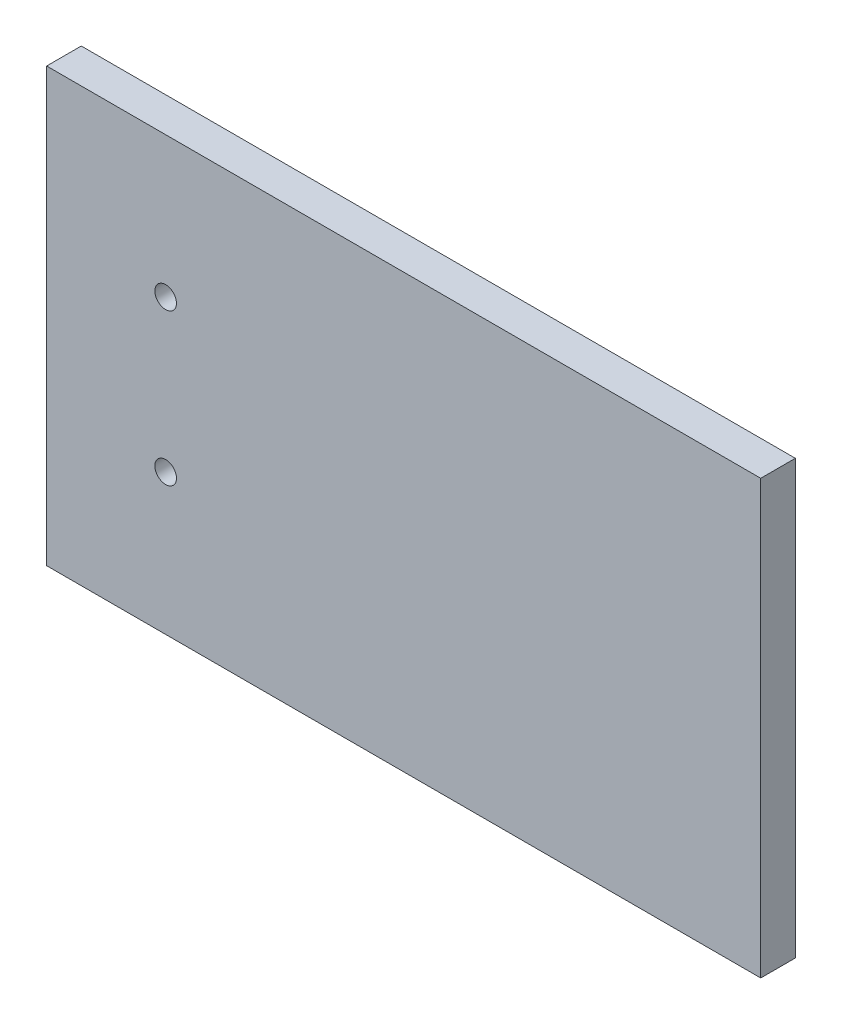
SolidWorks part; units mm, degrees
ref_plane "Front Plane" through (0, 0, 0) normal (0, 0, 1) x (1, 0, 0)
ref_plane "Top Plane" through (0, 0, 0) normal (0, 1, 0) x (1, 0, 0)
ref_plane "Right Plane" through (0, 0, 0) normal (1, 0, 0) x (0, 0, -1)
sketch "Sketch1" plane through (0, 0, 0) normal (0, 1, 0) x (1, 0, 0)
  line L0 (-6, 0) -> (6, 0) construction
  line L1 (6, -20) -> (-6, -20)
  line L2 (6, -20) -> (6, 20)
  line L3 (6, 20) -> (-6, 20)
  line L4 (-6, -20) -> (-6, 20)
  line L5 (6, -20) -> (-6, 20) construction
  line L6 (6, 20) -> (-6, -20) construction
  line L7 (0, -5) -> (0, 5) construction
  circle A0 centre (0, 5) radius 1
  circle A1 centre (0, -5) radius 1
  point P0 (0, 0)
  dimension "D3" = 5
  dimension "D4" = 2
  dimension "D1" = 40
  dimension "D2" = 12
extrude "Hinge " [suppressed] add sketch "Sketch1" along normal blind 5
sketch "Sketch2" [suppressed] plane through (6, 0, 0) normal (1, 0, 0) x (0, 0, -1)
  line L0 (0, 0) -> (0, 5) construction
  line L1 (-20, 0) -> (20, 0) construction
  line L2 (-20, 5) -> (20, 5) construction
  line L3 (-20, 2.5) -> (20, 2.5) construction
  line L4 (-20, 5) -> (-20, 0) construction
  line L5 (20, 5) -> (20, 0) construction
  line L7 (-6, 0) -> (-16, 0)
  line L8 (-6, 0) -> (-6, 5)
  line L9 (-6, 5) -> (-16, 5)
  line L10 (-16, 0) -> (-16, 5)
  line L11 (-6, 0) -> (-16, 5) construction
  line L12 (-6, 5) -> (-16, 0) construction
  line L13 (16, 0) -> (6, 0)
  line L14 (16, 0) -> (16, 5)
  line L15 (16, 5) -> (6, 5)
  line L16 (6, 0) -> (6, 5)
  line L17 (16, 0) -> (6, 5) construction
  line L18 (16, 5) -> (6, 0) construction
  point P12 (-11, 2.5)
  point P17 (11, 2.5)
  dimension "D1" = 6
  dimension "D2" = 5
  dimension "D3" = 10
extrude "Hinge Extrude 1" [suppressed] add sketch "Sketch2" along normal blind 5
sketch "Sketch3" [suppressed] plane through (0, 0, -16) normal (0, 0, -1) x (-1, 0, 0)
  line L0 (-8.5, 0) -> (-8.5, 5) construction
  line L1 (-11, 0) -> (-6, 0) construction
  line L2 (-11, 5) -> (-6, 5) construction
  circle A0 centre (-8.5, 2.5) radius 1
  dimension "D1" = 2
extrude "Hole Cut 1" [suppressed] cut sketch "Sketch3" against normal through all both and the other way through all
fillet "Fillet Holes 1" [suppressed] radius 0.5
chamfer "Chamfer 1" [suppressed] distance 1.5 angle 45
sketch "Sketch4" [suppressed] plane through (6, 0, 0) normal (1, 0, 0) x (0, 0, -1)
  line L0 (0, 0) -> (0, 5) construction
  line L1 (-20, 0) -> (20, 0) construction
  line L2 (-20, 5) -> (20, 5) construction
  line L4 (5, 0) -> (-5, 0)
  line L5 (5, 0) -> (5, 5)
  line L6 (5, 5) -> (-5, 5)
  line L7 (-5, 0) -> (-5, 5)
  line L8 (5, 0) -> (-5, 5) construction
  line L9 (5, 5) -> (-5, 0) construction
  point P6 (0, 2.5)
  dimension "D1" = 5
  dimension "D2" = 10
extrude "Hinge Extrude 2" [suppressed] add sketch "Sketch4" along normal blind 5
sketch "Sketch6" [suppressed] plane through (0, 0, -5) normal (0, 0, -1) x (-1, 0, 0)
  line L0 (-8.5, 0) -> (-8.5, 5) construction
  line L1 (-11, 0) -> (-6, 0) construction
  line L2 (-11, 5) -> (-6, 5) construction
  circle A0 centre (-8.5, 2.5) radius 1
  dimension "D1" = 2
extrude "Hole Cut 2 " [suppressed] cut sketch "Sketch6" against normal through all
chamfer "Chamfer2" [suppressed] distance 1.5 angle 45
fillet "Fillet Holes 2" [suppressed] radius 0.5
sketch "Sketch7" [suppressed] plane through (0, 0, 0) normal (0, 0, 1) x (1, 0, 0)
  circle A0 centre (0, 0) radius 1
  dimension "D1" = 2
extrude "Hinge Bar" [suppressed] add sketch "Sketch7" along normal blind 42
sketch "Sketch8" [suppressed] plane through (0, 0, 0) normal (0, 0, -1) x (-1, 0, 0)
  circle A0 centre (0, 0) radius 1.5
  dimension "D1" = 3
extrude "Hinge Bar Holder" [suppressed] add sketch "Sketch8" along normal blind 1
chamfer "Hinge Bar Holder Fillet" [suppressed] distance 0.5 angle 45
sketch "Sketch9" plane through (0, 0, 0) normal (1, 0, 0) x (0, 0, -1)
  circle A0 centre (0, 0) radius 1.5
  dimension "D1" = 3
extrude "Hinge Bar Cap" [suppressed] add sketch "Sketch9" along normal blind 2
chamfer "Hinge Bar Cap Fillet" [suppressed] distance 0.5 angle 45
sketch "Sketch10" [suppressed] plane through (2, 0, 0) normal (1, 0, 0) x (0, 0, -1)
  circle A0 centre (0, 0) radius 1
  dimension "D1" = 2
extrude "Hinge Bar Cap Cut" [suppressed] cut sketch "Sketch10" against normal blind 1
sketch "Sketch11" plane through (0, 0, 0) normal (0, 0, 1) x (1, 0, 0)
  line L1 (-33, 20) -> (33, 20)
  line L2 (-33, 20) -> (-33, -20)
  line L3 (-33, -20) -> (33, -20)
  line L4 (33, 20) -> (33, -20)
  line L5 (-33, 20) -> (33, -20) construction
  line L6 (-33, -20) -> (33, 20) construction
  point P0 (0, 0)
  dimension "D1" = 40
  dimension "D2" = 66
extrude "Hole Side Thing" add sketch "Sketch11" along normal blind 3.2
sketch "Sketch12" plane through (0, 0, 3.2) normal (0, 0, 1) x (1, 0, 0)
  line L0 (0, 0) -> (-33, 0) construction
  line L1 (-33, 20) -> (-33, -20) construction
  circle A0 centre (-22, 7) radius 1
  circle A1 centre (-22, -7) radius 1
  dimension "D1" = 2
  dimension "D3" = 11
  dimension "D2" = 7
extrude "Holes for Hole Side Thing" cut sketch "Sketch12" against normal blind 3.2
